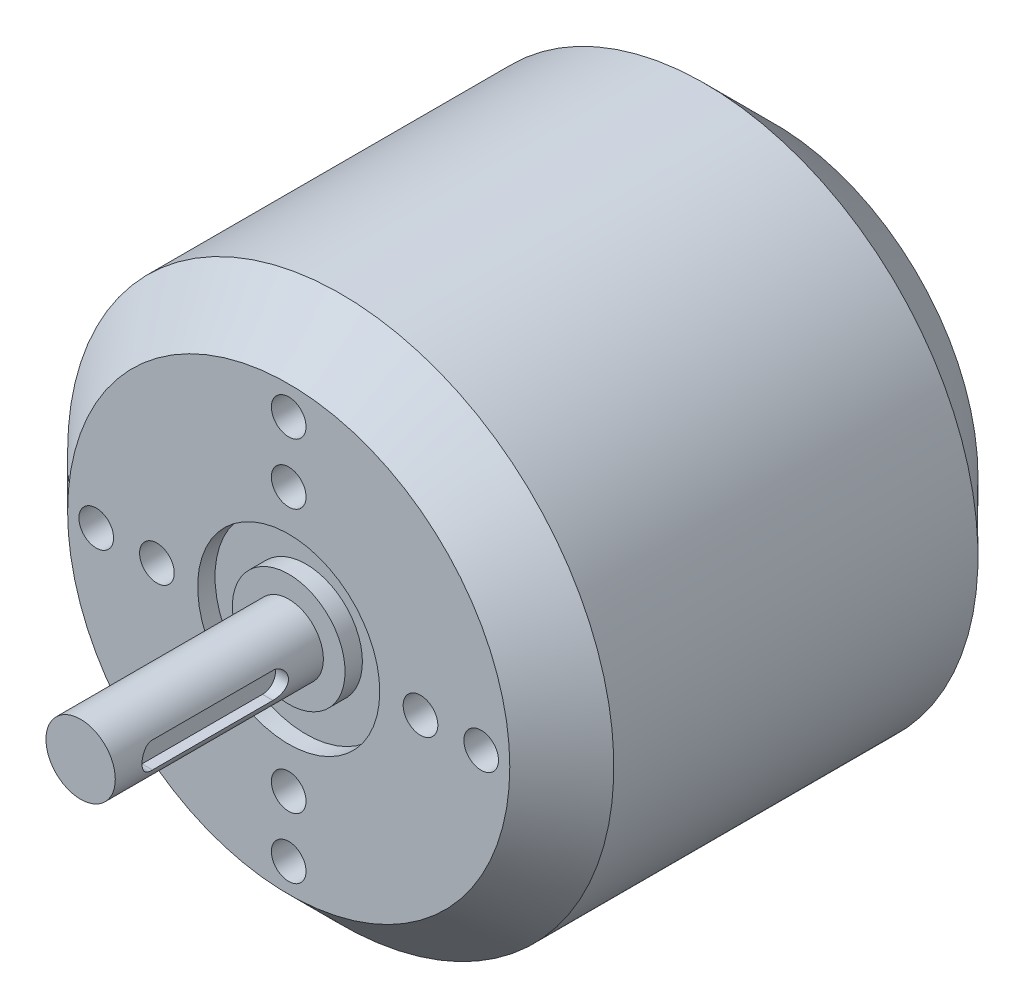
SolidWorks part; units mm, degrees
material "6061-T6 (SS)"
ref_plane "Front Plane" through (0, 0, 0) normal (0, 0, 1) x (1, 0, 0)
ref_plane "Top Plane" through (0, 0, 0) normal (0, 1, 0) x (1, 0, 0)
ref_plane "Right Plane" through (0, 0, 0) normal (1, 0, 0) x (0, 0, -1)
sketch "Sketch1" plane through (0, 0, 0) normal (0, 0, 1) x (1, 0, 0)
  circle A0 centre (0, 0) radius 31.5
  dimension "D1" = 63
extrude "Boss-Extrude1" add sketch "Sketch1" along normal blind 42
sketch "Sketch2" plane through (0, 0, 42) normal (0, 0, 1) x (1, 0, 0)
  circle A0 centre (0, 0) radius 31.5
extrude "Boss-Extrude2" add sketch "Sketch2" along normal blind 6
chamfer "Chamfer1" distance 6 distance2 6 1 edges at (31.5, 0, 48)
ref_plane "Plane1" through (0, 0, 33) normal (0, 0, 1) x (1, 0, 0)
sketch "Sketch4" plane through (0, 0, 0) normal (0, 0, -1) x (-1, 0, 0)
  circle A0 centre (0, 0) radius 31.5
extrude "Boss-Extrude3" add sketch "Sketch4" along normal blind 8
ref_plane "Plane2" through (0, 0, 2) normal (0, 0, -1) x (-1, 0, 0)
chamfer "Chamfer2" distance 8 distance2 8 1 edges at (-31.5, 0, -8)
sketch "Sketch6" plane through (0, 0, -8) normal (0, 0, -1) x (-1, 0, 0)
  circle A0 centre (0, 0) radius 7.5
  dimension "D1" = 15
extrude "Boss-Extrude4" add sketch "Sketch6" along normal blind 1
sketch "Sketch7" plane through (0, 0, 48) normal (0, 0, 1) x (1, 0, 0)
  circle A0 centre (0, 0) radius 4
  dimension "D1" = 8
extrude "Boss-Extrude5" add sketch "Sketch7" along normal blind 24
sketch "Sketch10" plane through (0, 0, 48) normal (0, 0, 1) x (1, 0, 0)
  circle A0 centre (0, 15.2) radius 2
  circle A1 centre (0, 22.2) radius 2
  circle A2 centre (22.2, 0) radius 2
  circle A3 centre (15.2, 0) radius 2
  circle A4 centre (0, -22.2) radius 2
  circle A5 centre (0, -15.2) radius 2
  circle A6 centre (-22.2, 0) radius 2
  circle A7 centre (-15.2, 0) radius 2
  point P20 (0, 0)
  dimension "D1" = 4
  dimension "D2" = 4
  dimension "D4" = 22.2
  dimension "D3" = 15.2
  dimension "D5" = 4
extrude "Cut-Extrude4" cut sketch "Sketch10" against normal blind 8
ref_axis "Hip_Axis_b" through (0, 0, 42) along (0, 0, -1)
ref_plane "Plane3" through (2.5, 0, 0) normal (1, 0, 0) x (0, 0, -1)
sketch "Sketch11" plane through (2.5, 0, 0) normal (1, 0, 0) x (0, 0, -1)
  line L0 (-67.4185, 0) -> (-53.5271, 0) construction
  line L1 (-67.4185, 1.5) -> (-53.5271, 1.5)
  line L2 (-67.4185, -1.5) -> (-53.5271, -1.5)
  arc A0 (-67.4185, 1.5) -> (-67.4185, -1.5) centre (-67.4185, 0) ccw
  arc A1 (-53.5271, -1.5) -> (-53.5271, 1.5) centre (-53.5271, 0) ccw
  point P3 (-60.4728, 0)
  dimension "D1" = 3
extrude "Cut-Extrude5" cut sketch "Sketch11" along normal blind 10
sketch "Sketch12" plane through (0, 0, 48) normal (0, 0, 1) x (1, 0, 0)
  circle A0 centre (0, 0) radius 6.5
  circle A1 centre (0, 0) radius 10.5
  dimension "D1" = 21
  dimension "D2" = 13
extrude "Cut-Extrude6" cut sketch "Sketch12" against normal blind 2
